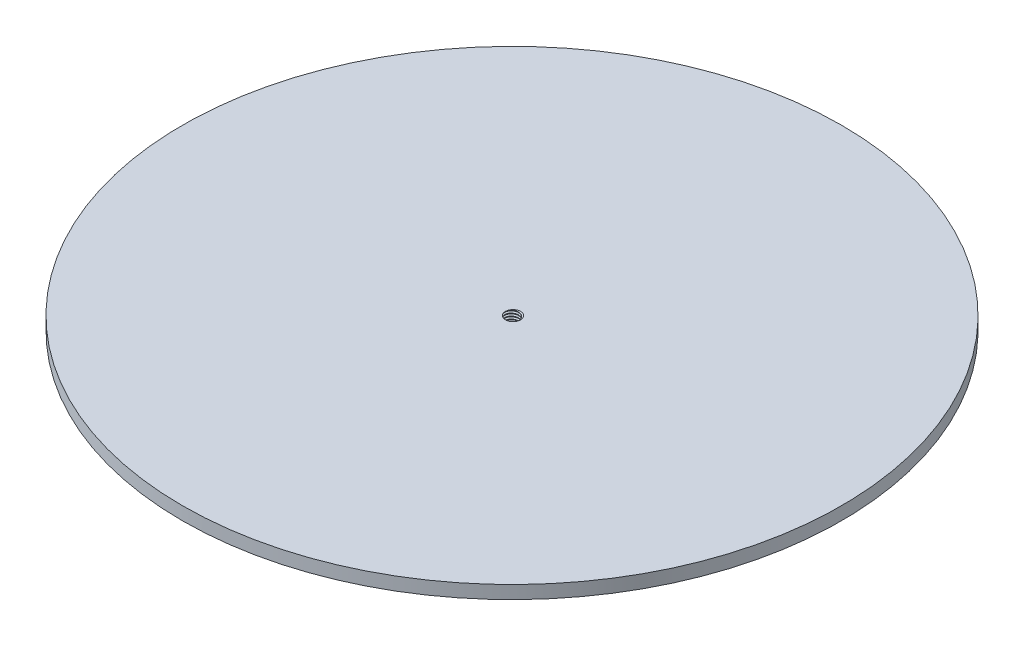
SolidWorks part; units mm, degrees
material "6061 Alloy"
ref_plane "Front Plane" through (0, 0, 0) normal (0, 0, 1) x (1, 0, 0)
ref_plane "Top Plane" through (0, 0, 0) normal (0, 1, 0) x (1, 0, 0)
ref_plane "Right Plane" through (0, 0, 0) normal (1, 0, 0) x (0, 0, -1)
sketch "Sketch1" plane through (0, 0, 0) normal (0, 1, 0) x (1, 0, 0)
  circle A0 centre (0, 0) radius 160
  dimension "D1" = 320
extrude "Boss-Extrude1" add sketch "Sketch1" along normal blind 6.35
sketch "Sketch7" plane through (0, 0, 0) normal (0, -1, 0) x (1, 0, 0)
  circle A0 centre (0, 0) radius 3.3234
  dimension "D1" = 6.6468
extrude "Cut-Extrude1" cut sketch "Sketch7" against normal through all
sketch "Sketch10" plane through (0, 0, 0) normal (0, 0, 1) x (1, 0, 0)
  line L0 (-3.0528, 0) -> (-4.1353, -0.625) construction
  line L1 (-4.1353, -0.625) -> (-3.0528, -1.25) construction
  line L2 (-3.0528, -1.25) -> (-3.0528, 0) construction
  line L3 (-4.1353, -0.625) -> (-3.0528, -0.625) construction
  line L4 (0, 0) -> (0, -2.9583) construction
  line L5 (-3.1856, -0.0767) -> (-4, -0.5469)
  line L6 (-4, -0.5469) -> (-4, -0.7031)
  line L7 (-4, -0.7031) -> (-3.1856, -1.1733)
  line L8 (-3.3234, 0) -> (3.3234, 0) construction
  line L9 (-3.1856, -0.0767) -> (-3.1856, -1.1733)
  dimension "D1" = 60
  dimension "D2" = 1.0825
  dimension "D3" = 4
  dimension "D4" = 0.1353
sketch "Sketch11" plane through (0, 0, 0) normal (0, -1, 0) x (1, 0, 0)
  circle A0 centre (0, 0) radius 4
  dimension "D1" = 8
curve "Helix/Spiral3" pitch 1.25 height 8.75 radius 4 centre (0, 0, 0) axis (0, 1, 0) start towards (0, 0, -1)
sweep "Cut-Sweep1" cut profiles "Sketch10" path "Helix/Spiral3"
equation "\"rod_diameter\"= 8"
equation "\"rod_hole_thickness\"= 4"
equation "\"rod_radius\"= \"rod_diameter\" / 2"
equation "\"platter_diameter\"= 320"
equation "\"platter_radius\"= \"platter_diameter\" / 2"
equation "\"extruder_mount_hole_spacing\"= 75"
equation "\"arm_rod_spacing\"= 40"
equation "\"top_frame_spacing\"= 100"
equation "\"motor_level_rod_spacing\"= 15"
equation "\"linear_bearing_diameter\"= 15"
equation "\"z_rod_spacing\"= 75"
equation "\"z_drive_rod_offset\"= 12"
equation "\"platter_rod_spacing\"= 50"
equation "\"rod_nut_thickness\"= 6.5"
equation "\"rod_nut_inscribed_diameter\"= 13"
equation "\"z_height\"= 400"
equation "\"gear_pitch\"=2"
equation "\"r_gear_teeth\"= 450"
equation "\"theta_gear_teeth\"= 385"
equation "\"sheet_thickness\"=5.333"
equation "\"sheet_tab_hole_thickness\"= \"sheet_thickness\""
equation "\"sheet_tab_width\"= \"sheet_thickness\"*2"
equation "\"sheet_double_tab_width\"= 35"
equation "\"sheet_bolt_diameter\"= 3"
equation "\"sheet_bolt_length\"= 16"
equation "\"sheet_nut_diameter\"= 5.5"
equation "\"sheet_nut_thickness\"= 2.5"
equation "\"sheet_nut_depth\"= 10"
equation "\"bearing_outside_diameter\"= 22"
equation "\"bearing_thickness\"= 7"
equation "\"corner_part_thickness\"= \"sheet_thickness\" + \"bearing_thickness\""
equation "\"setscrew_nut_diameter\"= 6"
equation "\"setscrew_nut_thickness\"= 3"
equation "\"setscrew_bolt_diameter\"= 3"
equation "\"motor_shaft_diameter\"= 5.7"
equation "\"printed_hole_tolerance\"= 0.3"
equation "\"D1@Sketch1\"=\"platter_diameter\""
equation "\"P\"= 1.25"
equation "\"Dmaj\"=8"
equation "\"H\"= sqr ( 3 ) / 2 * \"P\""
equation "\"Dmin\"= \"Dmaj\" - 2 * ( 5 / 8 ) * \"H\""
equation "\"D1@Sketch7\"=\"Dmin\""
equation "\"D2@Sketch10\"=\"H\""
equation "\"D3@Sketch10\"=\"Dmaj\"/2"
equation "\"D4@Sketch10\"=\"H\"/8"
equation "\"D1@Sketch11\"=\"Dmaj\""
